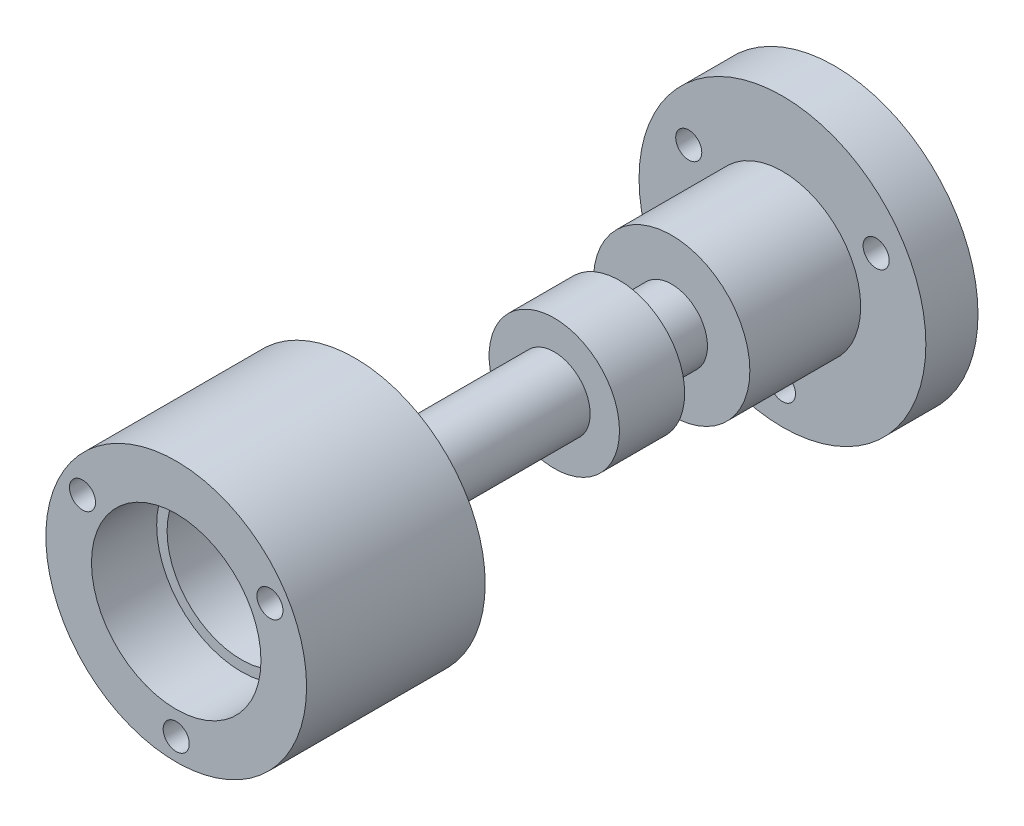
SolidWorks part; units mm, degrees
material "AISI 4340 Steel, normalized"
ref_plane "Front Plane" through (0, 0, 0) normal (0, 0, 1) x (1, 0, 0)
ref_plane "Top Plane" through (0, 0, 0) normal (0, 1, 0) x (1, 0, 0)
ref_plane "Right Plane" through (0, 0, 0) normal (1, 0, 0) x (0, 0, -1)
sketch "Sketch1" plane through (0, 0, 0) normal (0, 0, 1) x (1, 0, 0)
  circle A0 centre (0, 0) radius 11
extrude "Mounting_Flange" add sketch "Sketch1" along normal blind 4 from offset 4 offset against normal yes
sketch "Sketch2" plane through (0, 0, 0) normal (0, 0, 1) x (1, 0, 0)
  circle A0 centre (0, 0) radius 2.75
extrude "D5p5_Central_Post" add sketch "Sketch2" along normal blind 32.81
sketch "Sketch3" plane through (0, 0, 0) normal (0, 0, 1) x (1, 0, 0)
  circle A0 centre (0, 0) radius 10
extrude "Closed_Floor_Below_Shaft_Nose" add sketch "Sketch3" along normal blind 2.2 from offset 32.8
sketch "Sketch4" plane through (0, 0, 0) normal (0, 0, 1) x (1, 0, 0)
  circle A0 centre (0, 0) radius 10
  circle A1 centre (0, 0) radius 5.7
extrude "Shaft_And_Clip_Clearance" add sketch "Sketch4" along normal blind 6.5 from offset 35
sketch "Sketch5" plane through (0, 0, 0) normal (0, 0, 1) x (1, 0, 0)
  circle A0 centre (0, 0) radius 10
  circle A1 centre (0, 0) radius 6.5
extrude "Lower_686ZZ_Seat" add sketch "Sketch5" along normal blind 5 from offset 41.5
sketch "Sketch6" plane through (0, 0, -4) normal (0, 0, -1) x (-1, 0, 0)
  circle A0 centre (-7.188, 4.15) radius 1
  circle A1 centre (7.188, 4.15) radius 1
  circle A2 centre (0, -8.3) radius 1
extrude "Base_Three_M2_Through_Thread_Major_Envelopes" cut sketch "Sketch6" against normal blind 4.01
sketch "Sketch7" plane through (0, 0, 46.5) normal (0, 0, 1) x (1, 0, 0)
  circle A0 centre (7.188, 4.15) radius 1
  circle A1 centre (-7.188, 4.15) radius 1
  circle A2 centre (0, -8.3) radius 1
extrude "Top_Cap_Three_M2_Blind_Thread_Major_Envelopes" cut sketch "Sketch7" against normal blind 4.3
sketch "Sketch8" plane through (0, 0, 0) normal (0, 0, 1) x (1, 0, 0)
  circle A0 centre (0, 0) radius 6
extrude "Bench_D12_Root_To8p5" add sketch "Sketch8" along normal blind 8.5
sketch "Sketch9" plane through (0, 0, 0) normal (0, 0, 1) x (1, 0, 0)
  circle A0 centre (0, 0) radius 5
extrude "Bench_D10_Mid_Collar_12p5_To17p5" add sketch "Sketch9" along normal blind 5 from offset 12.5
